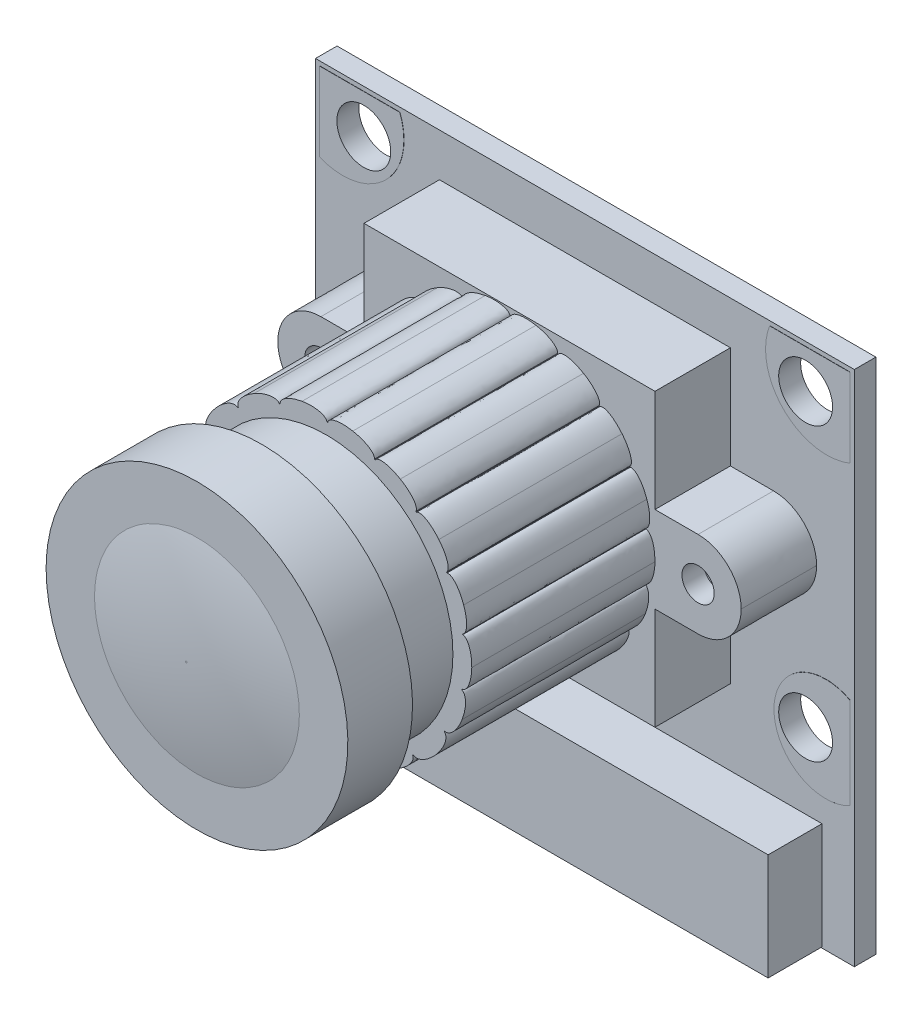
SolidWorks part; units mm, degrees
note: The reader was unsure of these and kept them because the rebuilt part matched: shared geometry of "Esboço1<3>", "Esboço1<5>", "Esboço1<7>", "Esboço1<8>", "Esboço7<11>", "Esboço9<3>".
ref_plane "Plano frontal" through (0, 0, 0) normal (0, 0, 1) x (1, 0, 0)
ref_plane "Plano superior" through (0, 0, 0) normal (0, 1, 0) x (1, 0, 0)
ref_plane "Plano direito" through (0, 0, 0) normal (1, 0, 0) x (0, 0, -1)
sketch "Esboço1" plane through (0, 0, 0) normal (0, 0, 1) x (1, 0, 0)
  line L0 (-12.5, -12) -> (12.5, -12)
  line L1 (12.5, -12) -> (12.5, 12)
  line L2 (12.5, 12) -> (-12.5, 12)
  line L3 (-12.5, 12) -> (-12.5, -12)
  line L4 (-6.75, -3.5) -> (6.75, -3.5)
  line L5 (6.75, -3.5) -> (6.75, 10)
  line L6 (6.75, 10) -> (-6.75, 10)
  line L7 (-6.75, 10) -> (-6.75, -3.5)
  line L8 (-8.7501, 5.25) -> (-6.75, 5.25)
  line L9 (-6.75, 5.25) -> (-6.75, 1.25)
  line L10 (-6.75, 1.25) -> (-8.7501, 1.25)
  line L11 (-10.75, 3.2499) -> (-10.75, 3.2501)
  line L12 (8.7501, 5.25) -> (6.75, 5.25)
  line L13 (6.75, 5.25) -> (6.75, 1.25)
  line L14 (6.75, 1.25) -> (8.7501, 1.25)
  line L15 (10.75, 3.2499) -> (10.75, 3.2501)
  line L20 (-12.3, 8.1438) -> (-12.3, 11.8)
  line L21 (-12.3, 11.8) -> (-8.5814, 11.8)
  line L22 (12.3, 8.1438) -> (12.3, 11.8)
  line L23 (12.3, 11.8) -> (8.5814, 11.8)
  line L24 (-12.3, -5.6234) -> (-12.3, -1.3766)
  line L25 (12.3, -5.6234) -> (12.3, -1.3766)
  line L26 (-6.2418, 2.1492) -> (-6.2429, 2.1492)
  line L27 (-6.2428, 2.1489) -> (-6.2418, 2.1492)
  ellipse E0 centre (-10.25, 10) end of major axis (-10.25, 11.25) minor radius 1.25
  ellipse E1 centre (10.25, 10) end of major axis (10.25, 11.25) minor radius 1.25
  ellipse E2 centre (10.25, -3.5) end of major axis (10.25, -2.25) minor radius 1.25
  ellipse E3 centre (-10.25, -3.5) end of major axis (-10.25, -2.25) minor radius 1.25
  ellipse E6 centre (-8.75, 3.25) end of major axis (-9.5, 3.25) minor radius 0.75
  ellipse E7 centre (8.75, 3.25) end of major axis (8, 3.25) minor radius 0.75
  spline S0 degree 3 poles (-8.7501, 1.25) (-9.8501, 1.25) (-10.75, 2.1499) (-10.75, 3.2499) knots 0.428571 0.428571 0.428571 0.428571 0.571429 0.571429 0.571429 0.571429
  spline S1 degree 3 poles (-10.75, 3.2501) (-10.75, 4.3501) (-9.8501, 5.25) (-8.7501, 5.25) knots 0.714286 0.714286 0.714286 0.714286 1 1 1 1
  spline S2 degree 3 poles (8.7501, 1.25) (9.8501, 1.25) (10.75, 2.1499) (10.75, 3.2499) knots 0.428571 0.428571 0.428571 0.428571 0.571429 0.571429 0.571429 0.571429
  spline S3 degree 3 poles (10.75, 3.2501) (10.75, 4.3501) (9.8501, 5.25) (8.7501, 5.25) knots 0.714286 0.714286 0.714286 0.714286 1 1 1 1
  spline S4 degree 3 poles (-8.5814, 11.8) (-8.4583, 11.4821) (-8.3907, 11.1366) (-8.3907, 10.7752) knots 0 0 0 0 0.166667 0.166667 0.166667 0.166667
  spline S5 degree 3 poles (-8.3907, 10.7752) (-8.3907, 9.2068) (-9.6621, 7.9353) (-11.2306, 7.9353) knots 0.166667 0.166667 0.166667 0.166667 0.333333 0.333333 0.333333 0.333333
  spline S6 degree 3 poles (-11.2306, 7.9353) (-11.609, 7.9353) (-11.9699, 8.0095) (-12.3, 8.1438) knots 0.333333 0.333333 0.333333 0.333333 0.5 0.5 0.5 0.5
  spline S7 degree 3 poles (8.5814, 11.8) (8.4583, 11.4821) (8.3907, 11.1366) (8.3907, 10.7752) knots 0 0 0 0 0.166667 0.166667 0.166667 0.166667
  spline S8 degree 3 poles (8.3907, 10.7752) (8.3907, 9.2068) (9.6621, 7.9353) (11.2306, 7.9353) knots 0.166667 0.166667 0.166667 0.166667 0.333333 0.333333 0.333333 0.333333
  spline S9 degree 3 poles (11.2306, 7.9353) (11.609, 7.9353) (11.9699, 8.0095) (12.3, 8.1438) knots 0.333333 0.333333 0.333333 0.333333 0.5 0.5 0.5 0.5
  spline S10 degree 3 poles (-11.1809, -1.1) (-9.8554, -1.1) (-8.7809, -2.1745) (-8.7809, -3.5) knots 0 0 0 0 0.166667 0.166667 0.166667 0.166667
  spline S11 degree 3 poles (-8.7809, -3.5) (-8.7809, -4.8255) (-9.8554, -5.9) (-11.1809, -5.9) knots 0.166667 0.166667 0.166667 0.166667 0.333333 0.333333 0.333333 0.333333
  spline S12 degree 3 poles (-11.1809, -5.9) (-11.5851, -5.9) (-11.9658, -5.7999) (-12.3, -5.6234) knots 0.333333 0.333333 0.333333 0.333333 0.5 0.5 0.5 0.5
  spline S13 degree 3 poles (-12.3, -1.3766) (-11.9658, -1.2001) (-11.5851, -1.1) (-11.1809, -1.1) knots 0.666667 0.666667 0.666667 0.666667 1 1 1 1
  spline S14 degree 3 poles (11.1809, -1.1) (9.8554, -1.1) (8.7809, -2.1745) (8.7809, -3.5) knots 0 0 0 0 0.166667 0.166667 0.166667 0.166667
  spline S15 degree 3 poles (8.7809, -3.5) (8.7809, -4.8255) (9.8554, -5.9) (11.1809, -5.9) knots 0.166667 0.166667 0.166667 0.166667 0.333333 0.333333 0.333333 0.333333
  spline S16 degree 3 poles (11.1809, -5.9) (11.5851, -5.9) (11.9658, -5.7999) (12.3, -5.6234) knots 0.333333 0.333333 0.333333 0.333333 0.5 0.5 0.5 0.5
  spline S17 degree 3 poles (12.3, -1.3766) (11.9658, -1.2001) (11.5851, -1.1) (11.1809, -1.1) knots 0.666667 0.666667 0.666667 0.666667 1 1 1 1
extrude "Ressalto-extrusão1" add sketch "Esboço1" against normal blind 1 contours L2 L3 L0 L1
extrude "Ressalto-extrusão2" add sketch "Esboço1<3>" along normal blind 3.5 contours L10 S0 L11 S1 L8 L9 | L12 L13 L14 S2 L15 S3 | L7 L4 L5 L6
sketch "Esboço1<3>" plane through (0, 0, 0) normal (0, 0, 1) x (1, 0, 0) same geometry as "Esboço1"
extrude "Corte-extrusão1" cut sketch "Esboço1<5>" along normal blind 3.5 and the other way blind 1 contours E6 | E7
sketch "Esboço1<5>" plane through (0, 0, 0) normal (0, 0, 1) x (1, 0, 0) same geometry as "Esboço1"
extrude "Ressalto-extrusão3" add sketch "Esboço1<7>" along normal blind 0.01 contours S7 S8 S9 L22 L23 | L21 S4 S5 S6 L20 | S17 S14 S15 S16 L25 | L24 S13 S10 S11 S12
sketch "Esboço1<7>" plane through (0, 0, 0) normal (0, 0, 1) x (1, 0, 0) same geometry as "Esboço1"
ref_plane "Plano2" through (0, 0, -1) normal (0, 0, -1) x (-1, 0, 0)
sketch "Esboço2" plane through (0, 0, -1) normal (0, 0, -1) x (-1, 0, 0)
  line L20 (-12.3, 8.1438) -> (-12.3, 11.8)
  line L21 (-12.3, 11.8) -> (-8.5814, 11.8)
  line L22 (12.3, 8.1438) -> (12.3, 11.8)
  line L23 (12.3, 11.8) -> (8.5814, 11.8)
  line L24 (-12.3, -5.6234) -> (-12.3, -1.3766)
  line L25 (12.3, -5.6234) -> (12.3, -1.3766)
  spline S4 degree 3 poles (-8.5814, 11.8) (-8.4583, 11.4821) (-8.3907, 11.1366) (-8.3907, 10.7752) knots 0 0 0 0 0.166667 0.166667 0.166667 0.166667
  spline S5 degree 3 poles (-8.3907, 10.7752) (-8.3907, 9.2068) (-9.6621, 7.9353) (-11.2306, 7.9353) knots 0.166667 0.166667 0.166667 0.166667 0.333333 0.333333 0.333333 0.333333
  spline S6 degree 3 poles (-11.2306, 7.9353) (-11.609, 7.9353) (-11.9699, 8.0095) (-12.3, 8.1438) knots 0.333333 0.333333 0.333333 0.333333 0.5 0.5 0.5 0.5
  spline S7 degree 3 poles (8.5814, 11.8) (8.4583, 11.4821) (8.3907, 11.1366) (8.3907, 10.7752) knots 0 0 0 0 0.166667 0.166667 0.166667 0.166667
  spline S8 degree 3 poles (8.3907, 10.7752) (8.3907, 9.2068) (9.6621, 7.9353) (11.2306, 7.9353) knots 0.166667 0.166667 0.166667 0.166667 0.333333 0.333333 0.333333 0.333333
  spline S9 degree 3 poles (11.2306, 7.9353) (11.609, 7.9353) (11.9699, 8.0095) (12.3, 8.1438) knots 0.333333 0.333333 0.333333 0.333333 0.5 0.5 0.5 0.5
  spline S10 degree 3 poles (-11.1809, -1.1) (-9.8554, -1.1) (-8.7809, -2.1745) (-8.7809, -3.5) knots 0 0 0 0 0.166667 0.166667 0.166667 0.166667
  spline S11 degree 3 poles (-8.7809, -3.5) (-8.7809, -4.8255) (-9.8554, -5.9) (-11.1809, -5.9) knots 0.166667 0.166667 0.166667 0.166667 0.333333 0.333333 0.333333 0.333333
  spline S12 degree 3 poles (-11.1809, -5.9) (-11.5851, -5.9) (-11.9658, -5.7999) (-12.3, -5.6234) knots 0.333333 0.333333 0.333333 0.333333 0.5 0.5 0.5 0.5
  spline S13 degree 3 poles (-12.3, -1.3766) (-11.9658, -1.2001) (-11.5851, -1.1) (-11.1809, -1.1) knots 0.666667 0.666667 0.666667 0.666667 1 1 1 1
  spline S14 degree 3 poles (11.1809, -1.1) (9.8554, -1.1) (8.7809, -2.1745) (8.7809, -3.5) knots 0 0 0 0 0.166667 0.166667 0.166667 0.166667
  spline S15 degree 3 poles (8.7809, -3.5) (8.7809, -4.8255) (9.8554, -5.9) (11.1809, -5.9) knots 0.166667 0.166667 0.166667 0.166667 0.333333 0.333333 0.333333 0.333333
  spline S16 degree 3 poles (11.1809, -5.9) (11.5851, -5.9) (11.9658, -5.7999) (12.3, -5.6234) knots 0.333333 0.333333 0.333333 0.333333 0.5 0.5 0.5 0.5
  spline S17 degree 3 poles (12.3, -1.3766) (11.9658, -1.2001) (11.5851, -1.1) (11.1809, -1.1) knots 0.666667 0.666667 0.666667 0.666667 1 1 1 1
extrude "Ressalto-extrusão4" add sketch "Esboço2" along normal blind 0.01
extrude "Corte-extrusão3" cut sketch "Esboço1<8>" against normal blind 1.2 and the other way blind 0.2 contours E1 | E0 | E2 | E3
sketch "Esboço1<8>" plane through (0, 0, 0) normal (0, 0, 1) x (1, 0, 0) same geometry as "Esboço1"
sketch "Esboço3" plane through (0, 0, 0) normal (0, 0, 1) x (1, 0, 0)
  line L16 (-11.0001, -11.95) -> (11, -11.95)
  line L17 (11, -11.95) -> (11, -7)
  line L18 (11, -7) -> (-11, -7)
  line L19 (-11, -7) -> (-11.0001, -11.95)
  point P4 (-11, -7)
extrude "Ressalto-extrusão5" add sketch "Esboço3" along normal blind 2.5
ref_plane "Plano3" through (0, 0, 3.5) normal (0, 0, 1) x (1, 0, 0)
sketch "Esboço5" plane through (0, 0, 3.5) normal (0, 0, 1) x (1, 0, 0)
  line L0 (-6.3119, 4.3557) -> (-6.3057, 4.3726)
  line L1 (-6.3057, 4.3726) -> (-6.3057, 4.3905)
  line L2 (-5.5493, 6.4576) -> (-5.5378, 6.4713)
  line L3 (-5.5378, 6.4713) -> (-5.5316, 6.4883)
  line L4 (-4.111, 8.1696) -> (-4.0953, 8.1786)
  line L5 (-4.0953, 8.1786) -> (-4.0838, 8.1922)
  line L6 (-2.1718, 9.2831) -> (-2.154, 9.2861)
  line L7 (-2.154, 9.2861) -> (-2.1385, 9.2949)
  line L8 (0.0318, 9.6624) -> (0.0495, 9.6591)
  line L9 (0.0495, 9.6591) -> (0.0671, 9.6621)
  line L10 (2.2315, 9.2614) -> (2.2472, 9.2521)
  line L11 (2.2472, 9.2521) -> (2.2645, 9.2489)
  line L12 (4.1596, 8.1289) -> (4.1712, 8.1148)
  line L13 (4.1712, 8.1148) -> (4.1863, 8.1059)
  line L14 (5.5811, 6.4028) -> (5.5871, 6.3857)
  line L15 (5.5871, 6.3857) -> (5.5983, 6.372)
  line L16 (6.3229, 4.2934) -> (6.3226, 4.2753)
  line L17 (6.3226, 4.2753) -> (6.3285, 4.2586)
  line L18 (6.2947, 2.0576) -> (6.2882, 2.0406)
  line L19 (6.2882, 2.0406) -> (6.288, 2.023)
  line L20 (5.4999, -0.0324) -> (5.4881, -0.0461)
  line L21 (5.4881, -0.0461) -> (5.4817, -0.0626)
  line L22 (4.0353, -1.7221) -> (4.0196, -1.7308)
  line L23 (4.0196, -1.7308) -> (4.0079, -1.7443)
  line L24 (2.0793, -2.8056) -> (2.0616, -2.8084)
  line L25 (2.0616, -2.8084) -> (2.0459, -2.8169)
  line L26 (-0.1299, -3.1509) -> (-0.1475, -3.1474)
  line L27 (-0.1475, -3.1474) -> (-0.1652, -3.1502)
  line L28 (-2.3232, -2.7162) -> (-2.3387, -2.7068)
  line L29 (-2.3387, -2.7068) -> (-2.3561, -2.7033)
  line L30 (-4.2336, -1.5541) -> (-4.2448, -1.5401)
  line L31 (-4.2448, -1.5401) -> (-4.2601, -1.5307)
  line L32 (-5.6284, 0.1935) -> (-5.6341, 0.2107)
  line L33 (-5.6341, 0.2107) -> (-5.6453, 0.2246)
  spline S0 degree 3 poles (-6.4503, 2.2141) (-6.6245, 2.3629) (-6.7498, 2.7727) (-6.7498, 3.2551) knots 0 0 0 0 0.014085 0.014085 0.014085 0.014085
  spline S1 degree 3 poles (-6.7498, 3.2551) (-6.7498, 3.858) (-6.5543, 4.3475) (-6.3119, 4.3557) knots 0.014085 0.014085 0.014085 0.014085 0.028169 0.028169 0.028169 0.028169
  spline S2 degree 3 poles (-6.3057, 4.3905) (-6.5305, 4.4815) (-6.5459, 5.0084) (-6.3388, 5.5746) knots 0.056338 0.056338 0.056338 0.056338 0.070423 0.070423 0.070423 0.070423
  spline S3 degree 3 poles (-6.3388, 5.5746) (-6.1316, 6.1407) (-5.7798, 6.5333) (-5.5493, 6.4576) knots 0.070423 0.070423 0.070423 0.070423 0.084507 0.084507 0.084507 0.084507
  spline S4 degree 3 poles (-5.5316, 6.4883) (-5.7114, 6.651) (-5.5449, 7.1511) (-5.1558, 7.6116) knots 0.112676 0.112676 0.112676 0.112676 0.126761 0.126761 0.126761 0.126761
  spline S5 degree 3 poles (-5.1558, 7.6116) (-4.7666, 8.072) (-4.3014, 8.3198) (-4.111, 8.1696) knots 0.126761 0.126761 0.126761 0.126761 0.140845 0.140845 0.140845 0.140845
  spline S6 degree 3 poles (-4.0838, 8.1922) (-4.1969, 8.4068) (-3.8685, 8.8193) (-3.3448, 9.118) knots 0.169014 0.169014 0.169014 0.169014 0.183099 0.183099 0.183099 0.183099
  spline S7 degree 3 poles (-3.3448, 9.118) (-2.8212, 9.4167) (-2.299, 9.4896) (-2.1718, 9.2831) knots 0.183099 0.183099 0.183099 0.183099 0.197183 0.197183 0.197183 0.197183
  spline S8 degree 3 poles (-2.1385, 9.2949) (-2.171, 9.5352) (-1.7209, 9.8098) (-1.1265, 9.9104) knots 0.225352 0.225352 0.225352 0.225352 0.239437 0.239437 0.239437 0.239437
  spline S9 degree 3 poles (-1.1265, 9.9104) (-0.5321, 10.0109) (-0.0168, 9.9) (0.0318, 9.6624) knots 0.239437 0.239437 0.239437 0.239437 0.253521 0.253521 0.253521 0.253521
  spline S10 degree 3 poles (0.0671, 9.6621) (0.1193, 9.8989) (0.6363, 10.0021) (1.229, 9.8923) knots 0.28169 0.28169 0.28169 0.28169 0.295775 0.295775 0.295775 0.295775
  spline S11 degree 3 poles (1.229, 9.8923) (1.8218, 9.7824) (2.2675, 9.5012) (2.2315, 9.2614) knots 0.295775 0.295775 0.295775 0.295775 0.309859 0.309859 0.309859 0.309859
  spline S12 degree 3 poles (2.2645, 9.2489) (2.3949, 9.4534) (2.9159, 9.3726) (3.4349, 9.0659) knots 0.338028 0.338028 0.338028 0.338028 0.352113 0.352113 0.352113 0.352113
  spline S13 degree 3 poles (3.4349, 9.0659) (3.9539, 8.759) (4.2758, 8.3419) (4.1596, 8.1289) knots 0.352113 0.352113 0.352113 0.352113 0.366197 0.366197 0.366197 0.366197
  spline S14 degree 3 poles (4.1863, 8.1059) (4.379, 8.2532) (4.8405, 7.9982) (5.2225, 7.5318) knots 0.394366 0.394366 0.394366 0.394366 0.408451 0.408451 0.408451 0.408451
  spline S15 degree 3 poles (5.2225, 7.5318) (5.6044, 7.0653) (5.7633, 6.5628) (5.5811, 6.4028) knots 0.408451 0.408451 0.408451 0.408451 0.422535 0.422535 0.422535 0.422535
  spline S16 degree 3 poles (5.5983, 6.372) (5.8298, 6.4441) (6.1756, 6.0461) (6.3741, 5.4769) knots 0.450704 0.450704 0.450704 0.450704 0.464789 0.464789 0.464789 0.464789
  spline S17 degree 3 poles (6.3741, 5.4769) (6.5724, 4.9076) (6.549, 4.3811) (6.3229, 4.2934) knots 0.464789 0.464789 0.464789 0.464789 0.478873 0.478873 0.478873 0.478873
  spline S18 degree 3 poles (6.3285, 4.2586) (6.5707, 4.2467) (6.7586, 3.7542) (6.7494, 3.1514) knots 0.507042 0.507042 0.507042 0.507042 0.521127 0.521127 0.521127 0.521127
  spline S19 degree 3 poles (6.7494, 3.1514) (6.7401, 2.5485) (6.5371, 2.0622) (6.2947, 2.0576) knots 0.521127 0.521127 0.521127 0.521127 0.535211 0.535211 0.535211 0.535211
  spline S20 degree 3 poles (6.288, 2.023) (6.5113, 1.9287) (6.5186, 1.4014) (6.3028, 0.8385) knots 0.56338 0.56338 0.56338 0.56338 0.577465 0.577465 0.577465 0.577465
  spline S21 degree 3 poles (6.3028, 0.8385) (6.0868, 0.2756) (5.7291, -0.1114) (5.4999, -0.0324) knots 0.577465 0.577465 0.577465 0.577465 0.591549 0.591549 0.591549 0.591549
  spline S22 degree 3 poles (5.4817, -0.0626) (5.6589, -0.228) (5.4847, -0.7256) (5.0886, -1.1801) knots 0.619718 0.619718 0.619718 0.619718 0.633803 0.633803 0.633803 0.633803
  spline S23 degree 3 poles (5.0886, -1.1801) (4.6923, -1.6346) (4.2233, -1.8752) (4.0353, -1.7221) knots 0.633803 0.633803 0.633803 0.633803 0.647887 0.647887 0.647887 0.647887
  spline S24 degree 3 poles (4.0079, -1.7443) (4.1174, -1.9606) (3.7829, -2.3678) (3.2547, -2.6585) knots 0.676056 0.676056 0.676056 0.676056 0.690141 0.690141 0.690141 0.690141
  spline S25 degree 3 poles (3.2547, -2.6585) (2.7264, -2.9492) (2.2033, -3.0139) (2.0793, -2.8056) knots 0.690141 0.690141 0.690141 0.690141 0.704225 0.704225 0.704225 0.704225
  spline S26 degree 3 poles (2.0459, -2.8169) (2.0745, -3.0577) (1.6203, -3.3253) (1.0245, -3.4167) knots 0.732394 0.732394 0.732394 0.732394 0.746479 0.746479 0.746479 0.746479
  spline S27 degree 3 poles (1.0245, -3.4167) (0.4285, -3.5081) (-0.085, -3.3891) (-0.1299, -3.1509) knots 0.746479 0.746479 0.746479 0.746479 0.760563 0.760563 0.760563 0.760563
  spline S28 degree 3 poles (-0.1652, -3.1502) (-0.2211, -3.3861) (-0.7396, -3.4813) (-1.3305, -3.3624) knots 0.788732 0.788732 0.788732 0.788732 0.802817 0.802817 0.802817 0.802817
  spline S29 degree 3 poles (-1.3305, -3.3624) (-1.9216, -3.2435) (-2.3629, -2.9553) (-2.3232, -2.7162) knots 0.802817 0.802817 0.802817 0.802817 0.816901 0.816901 0.816901 0.816901
  spline S30 degree 3 poles (-2.3561, -2.7033) (-2.4896, -2.9057) (-3.0093, -2.8169) (-3.5234, -2.5022) knots 0.84507 0.84507 0.84507 0.84507 0.859155 0.859155 0.859155 0.859155
  spline S31 degree 3 poles (-3.5234, -2.5022) (-4.0377, -2.1874) (-4.3531, -1.765) (-4.2336, -1.5541) knots 0.859155 0.859155 0.859155 0.859155 0.873239 0.873239 0.873239 0.873239
  spline S32 degree 3 poles (-4.2601, -1.5307) (-4.455, -1.6749) (-4.9126, -1.4129) (-5.2872, -0.9408) knots 0.901408 0.901408 0.901408 0.901408 0.915493 0.915493 0.915493 0.915493
  spline S33 degree 3 poles (-5.2872, -0.9408) (-5.6619, -0.4685) (-5.813, 0.0364) (-5.6284, 0.1935) knots 0.915493 0.915493 0.915493 0.915493 0.929577 0.929577 0.929577 0.929577
  spline S34 degree 3 poles (-5.6453, 0.2246) (-5.8779, 0.1561) (-6.2175, 0.5595) (-6.4071, 1.1316) knots 0.957746 0.957746 0.957746 0.957746 0.971831 0.971831 0.971831 0.971831
  spline S35 degree 3 poles (-6.4071, 1.1316) (-6.5588, 1.5896) (-6.5689, 2.0182) (-6.4503, 2.2141) knots 0.971831 0.971831 0.971831 0.971831 1 1 1 1
extrude "Ressalto-extrusão6" add sketch "Esboço5" along normal blind 8.5
ref_plane "Plano5" through (0, 0, 12) normal (0, 0, 1) x (1, 0, 0)
sketch "Esboço6" plane through (0, 0, 12) normal (0, 0, 1) x (1, 0, 0)
  ellipse E0 centre (0.0001, 3.2499) end of major axis (0.0001, 9.125) minor radius 5.8751
extrude "Ressalto-extrusão7" add sketch "Esboço6" along normal blind 3
ref_plane "Plano7" through (0, 0, 15) normal (0, 0, 1) x (1, 0, 0)
sketch "Esboço7" plane through (0, 0, 15) normal (0, 0, 1) x (1, 0, 0)
  ellipse E8 centre (0, 3.25) end of major axis (0, 10.25) minor radius 7
  ellipse E9 centre (0, 3.25) end of major axis (0, 8) minor radius 4.75
extrude "Ressalto-extrusão8" add sketch "Esboço7" along normal blind 3 contours E8 | E9
extrude "Ressalto-extrusão9" add sketch "Esboço7<11>" along normal blind 3.5 contours E9
sketch "Esboço7<11>" plane through (0, 0, 15) normal (0, 0, 1) x (1, 0, 0) same geometry as "Esboço7"
fillet "Filete1" radius 22.5 1 edges at (-4.75, 3.25, 18.5)
sketch "Esboço9" plane through (0, 0, -1) normal (0, 0, -1) x (-1, 0, 0)
  ellipse E0 centre (-8.75, 3.25) end of major axis (-8.75, 4.75) minor radius 1.5
  ellipse E1 centre (8.75, 3.25) end of major axis (8.75, 4.75) minor radius 1.5
  ellipse E2 centre (-8.75, 3.25) end of major axis (-9.5, 3.25) minor radius 0.75
  ellipse E3 centre (8.75, 3.25) end of major axis (8, 3.25) minor radius 0.75
extrude "Ressalto-extrusão10" add sketch "Esboço9" along normal blind 1 contours E0 | E1
fillet "Filete2" radius 0.8 2 edges at (8.75, 4.75, -2) (-8.75, 4.75, -2)
ref_plane "Plano9" through (0, 0, -2) normal (0, 0, -1) x (-1, 0, 0)
sketch "Esboço11" plane through (0, 0, -2) normal (0, 0, -1) x (-1, 0, 0)
  line L0 (-8.9351, 4.3451) -> (-8.565, 4.3451)
  line L1 (-8.565, 4.3451) -> (-8.565, 3.435)
  line L2 (-8.565, 3.435) -> (-7.6549, 3.435)
  line L3 (-7.6549, 3.435) -> (-7.6549, 3.0649)
  line L4 (-7.6549, 3.0649) -> (-8.565, 3.0649)
  line L5 (-8.565, 3.0649) -> (-8.565, 2.1549)
  line L6 (-8.565, 2.1549) -> (-8.9351, 2.1549)
  line L7 (-8.9351, 2.1549) -> (-8.9351, 3.0649)
  line L8 (-8.9351, 3.0649) -> (-9.8451, 3.0649)
  line L9 (-9.8451, 3.0649) -> (-9.8451, 3.435)
  line L10 (-9.8451, 3.435) -> (-8.9351, 3.435)
  line L11 (-8.9351, 3.435) -> (-8.9351, 4.3451)
  line L12 (8.5649, 4.3451) -> (8.935, 4.3451)
  line L13 (8.935, 4.3451) -> (8.935, 3.435)
  line L14 (8.935, 3.435) -> (9.8451, 3.435)
  line L15 (9.8451, 3.435) -> (9.8451, 3.0649)
  line L16 (9.8451, 3.0649) -> (8.935, 3.0649)
  line L17 (8.935, 3.0649) -> (8.935, 2.1549)
  line L18 (8.935, 2.1549) -> (8.5649, 2.1549)
  line L19 (8.5649, 2.1549) -> (8.5649, 3.0649)
  line L20 (8.5649, 3.0649) -> (7.6549, 3.0649)
  line L21 (7.6549, 3.0649) -> (7.6549, 3.435)
  line L22 (7.6549, 3.435) -> (8.5649, 3.435)
  line L23 (8.5649, 3.435) -> (8.5649, 4.3451)
extrude "Corte-extrusão4" cut sketch "Esboço11" against normal blind 0.9
chamfer "Chanfro1" distance 0.75 angle 45 4 edges at (-8.75, 2.1549, -1.1) (-9.8451, 3.25, -1.1) (-8.75, 4.3451, -1.1) (-7.6549, 3.25, -1.1)
chamfer "Chanfro2" distance 0.75 angle 45 4 edges at (8.75, 2.1549, -1.1) (7.6549, 3.25, -1.1) (9.8451, 3.25, -1.1) (8.75, 4.3451, -1.1)
extrude "Ressalto-extrusão11" add sketch "Esboço9<3>" against normal blind 3.5 contours E2 | E3
sketch "Esboço9<3>" plane through (0, 0, -1) normal (0, 0, -1) x (-1, 0, 0) same geometry as "Esboço9"
ref_plane "Plano12" through (0, -12, 0) normal (0, -1, 0) x (-1, 0, 0)
sketch "Esboço12" plane through (0, -12, 0) normal (0, -1, 0) x (-1, 0, 0)
  line L4 (5.75, -1.65) -> (-5.75, -1.65)
  line L5 (5.75, -1.65) -> (5.75, -0.85)
  line L6 (5.75, -0.85) -> (-5.75, -0.85)
  line L7 (-5.75, -1.65) -> (-5.75, -0.85)
  point P4 (0, -1.25)
  dimension "D1" = 11.5
  dimension "D2" = 0.8
extrude "Corte-extrusão5" cut sketch "Esboço12" against normal blind 3.5 contours L4 L7 L6 L5
